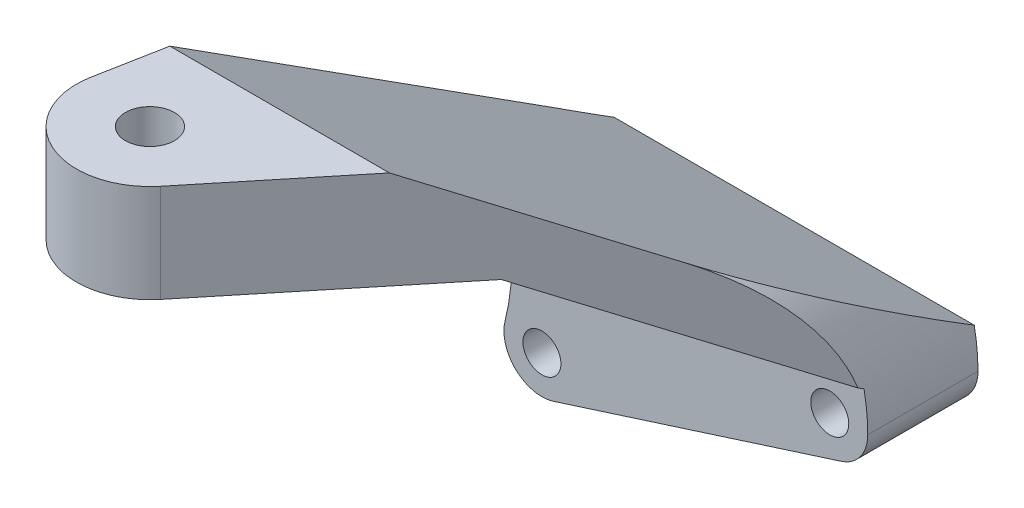
SolidWorks part; units mm, degrees
material "6061 Alloy"
ref_plane "Front Plane" through (0, 0, 0) normal (0, 0, 1) x (1, 0, 0)
ref_plane "Top Plane" through (0, 0, 0) normal (0, 1, 0) x (1, 0, 0)
ref_plane "Right Plane" through (0, 0, 0) normal (1, 0, 0) x (0, 0, -1)
sketch "Sketch1" plane through (0, 0, 0) normal (0, 0, 1) x (1, 0, 0)
  line L0 (26.6, 7.5073) -> (26.6, 10.6073)
  line L1 (0, 0) -> (23.5, 7.5073) construction
  line L6 (23.5, 7.5073) -> (0, 7.5073) construction
  line L7 (0, -55) -> (0, 55) construction
  line L8 (-3.1, 10.6073) -> (26.6, 10.6073)
  line L10 (0, 7.5073) -> (0, 0) construction
  line L11 (-3.1, 10.6073) -> (-3.1, 0)
  line L13 (24.4434, 4.5543) -> (0.9434, -2.953)
  circle A0 centre (0, 0) radius 1.55
  circle A2 centre (23.5, 7.5073) radius 1.55
  arc A3 (24.4434, 4.5543) -> (26.6, 7.5073) centre (23.5, 7.5073) ccw
  arc A4 (-3.1, 0) -> (0.9434, -2.953) centre (0, 0) ccw
  dimension "D2" = 3.1
  dimension "D3" = 6.2
  dimension "D1" = 24.67
  dimension "D4" = 3.1
  dimension "D6" = 23.5
extrude "Boss-Extrude1" add sketch "Sketch1" against normal blind 9
ref_plane "Plane1" through (0, 28, 0) normal (0, 1, 0) x (1, 0, 0)
sketch "Sketch7" plane through (0, 28, 0) normal (0, 1, 0) x (1, 0, 0)
  line L0 (0, -4.95) -> (0, 4.95) construction
  line L1 (-7.539, 0) -> (7.539, 0) construction
  line L3 (-3.1, 0) -> (-9.8952, 35.8836)
  line L4 (-3.1, 0) -> (26.6, 0)
  line L5 (26.6, 9) -> (0.6481, 40.794)
  line L6 (26.6, 9) -> (26.6, 0)
  circle A0 centre (-4, 37) radius 2
  arc A1 (0.6481, 40.794) -> (-9.8952, 35.8836) centre (-4, 37) ccw
  point P7 (-3.1, 0)
  point P8 (26.6, 0)
  dimension "D1" = 4
  dimension "D3" = 12
  dimension "D2" = 4
  dimension "D4" = 37
extrude "Boss-Extrude12" add sketch "Sketch7" against normal up to surface (17.3927 mm away) contours L3 A1 L5 L6 L4 up to face at (11.75, 10.6073, -4.5)
extrude "Cut-Extrude3" cut sketch "Sketch7<3>" against normal up to surface (17.3927 mm away) flip side to cut up to face at (1.8487, 10.6073, -19.7556)
sketch "Sketch7<3>" plane through (0, 28, 0) normal (0, 1, 0) x (1, 0, 0) same geometry as "Sketch7"
sketch "Sketch8" plane through (0, 0, 0) normal (1, 0, 0) x (0, 0, -1)
  line L0 (0, 10.6073) -> (30.5, 28)
  line L1 (0, 17.105) -> (0, -17.105) construction
  line L3 (13.6887, 28) -> (-13.6887, 28) construction
  line L4 (30.5, 28) -> (0, 28)
  line L5 (0, 28) -> (0, 10.6073)
  line L6 (37, 10.6073) -> (37, 28) construction
  line L7 (43, 20) -> (25.4712, 20)
  line L8 (43, 10.6073) -> (43, 28) construction
  line L9 (43, 20) -> (43, 10.6073)
  line L10 (43, 10.6073) -> (9, 10.6073)
  line L11 (9, 10.6073) -> (25.4712, 20)
  line L12 (9, 10.6073) -> (0, 10.6073) construction
  dimension "D1" = 6.5
  dimension "D2" = 8
  dimension "D3" = 4.4583
extrude "Cut-Extrude2" cut sketch "Sketch8" against normal mid plane 100
sketch "Sketch12" plane through (0, 0, 0) normal (0, 0, 1) x (1, 0, 0)
  line L1 (-7.9234, 20) -> (-4.8043, 10.6073) construction
  line L2 (20.13, 0) -> (-20.13, 0) construction
  line L3 (-10, 28) -> (-10, 20) construction
  line L4 (-3.1, 0) -> (-7.4936, 18.7056)
  arc A2 (-3.0088, 0.7463) -> (-3.1, 0) centre (0, 0) ccw
  arc A3 (-7.4936, 18.7056) -> (-3.0088, 0.7463) centre (-22.174, 5.5) cw
  dimension "D3" = 19.7459
  dimension "D2" = 12.174
  dimension "D1" = 5.5
extrude "Cut-Extrude5" cut sketch "Sketch12" against normal through all
sketch "Sketch14" plane through (0, 0, 0) normal (0, 0, 1) x (1, 0, 0)
  line L0 (26.6, 15.7395) -> (9.0506, 28) construction
  line L1 (19.8515, 20.4542) -> (26.6, 15.7395)
  line L2 (26.6, 15.7395) -> (26.6, 7.5073)
  arc A0 (26.6, 7.5073) -> (19.8515, 20.4542) centre (10.8064, 7.5073) ccw
extrude "Cut-Extrude7" cut sketch "Sketch14" against normal through all
mirror "Mirror9" about plane through (0, 0, 0) normal (0, 0, 1) of bodies 111
sketch "Sketch15" plane through (0, 0, 0) normal (0, 0, 1) x (1, 0, 0)
  line L1 (-11.2714, 28.977) -> (29.7742, 28.977)
  line L2 (-11.2714, 28.977) -> (-11.2714, -3.4246)
  line L3 (-11.2714, -3.4246) -> (29.7742, -3.4246)
  line L4 (29.7742, 28.977) -> (29.7742, -3.4246)
extrude "Cut-Extrude8" cut sketch "Sketch15" against normal through all
